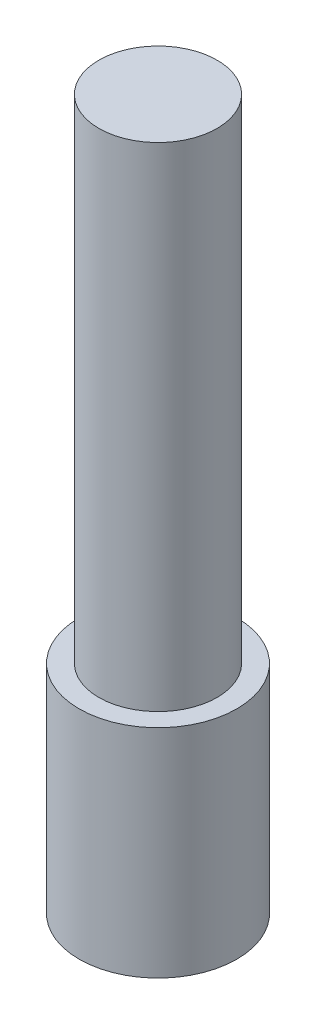
SolidWorks part; units mm, degrees
ref_plane "Front Plane" through (0, 0, 0) normal (0, 0, 1) x (1, 0, 0)
ref_plane "Top Plane" through (0, 0, 0) normal (0, 1, 0) x (1, 0, 0)
ref_plane "Right Plane" through (0, 0, 0) normal (1, 0, 0) x (0, 0, -1)
sketch "Sketch1" plane through (0, 0, 0) normal (0, 1, 0) x (1, 0, 0)
  circle A0 centre (0, 0) radius 15
  dimension "D1" = 30
sketch "Sketch2" plane through (0, 0, 0) normal (0, 1, 0) x (1, 0, 0)
  circle A0 centre (0, 0) radius 3
  dimension "D1" = 6
extrude "Boss-Extrude1" add sketch "Sketch2" along normal blind 25
sketch "Sketch3" plane through (0, 0, 0) normal (0, -1, 0) x (1, 0, 0)
  circle A0 centre (0, 0) radius 4
  dimension "D1" = 8
extrude "Boss-Extrude2" add sketch "Sketch3" along normal blind 11
